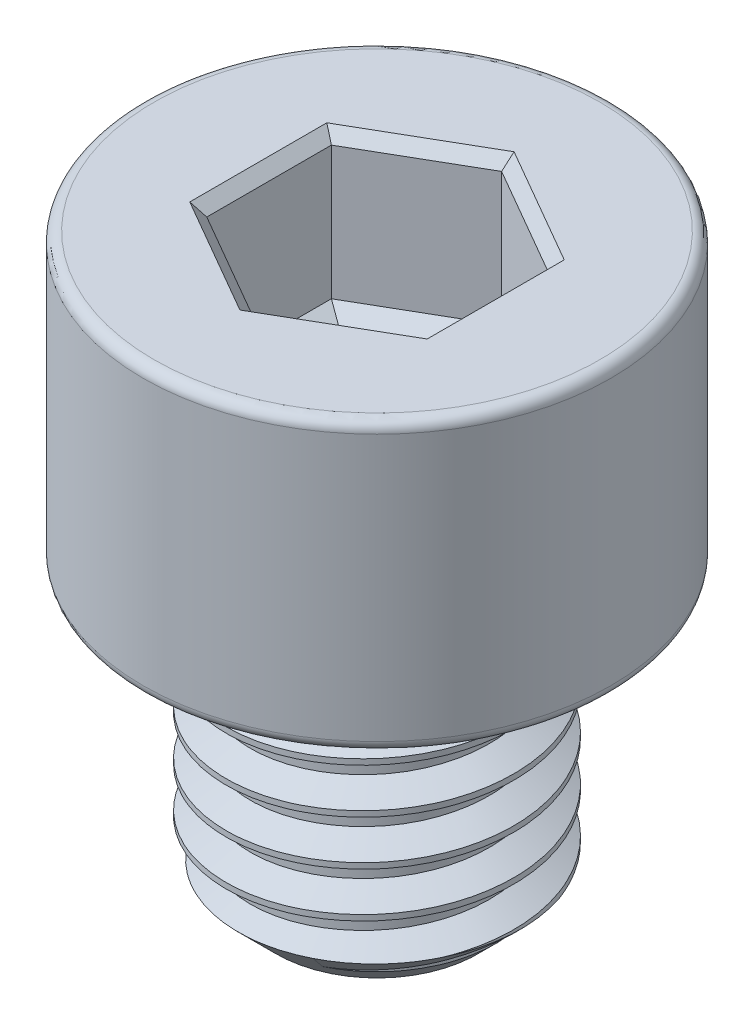
SolidWorks part; units mm, degrees
material "AISI Type A2 Tool Steel"
ref_plane "Front Plane" through (0, 0, 0) normal (0, 0, 1) x (1, 0, 0)
ref_plane "Top Plane" through (0, 0, 0) normal (0, 1, 0) x (1, 0, 0)
ref_plane "Right Plane" through (0, 0, 0) normal (1, 0, 0) x (0, 0, -1)
sketch "Sketch1" plane through (0, 0, 0) normal (0, 1, 0) x (1, 0, 0)
  circle A0 centre (0, 0) radius 4
  dimension "D1" = 8
extrude "Boss-Extrude1" add sketch "Sketch1" along normal blind 8
thread "Thread1" pitch 1.25 method cut profile "Thread Profile1" start angle 0, offset 1.25, length 0, pitch 1.25, diameter 8
ref_plane "Plane1" through (-4, 9.25, 0) normal (0, 0, 1) x (-1, 0, 0)
sketch "Thread Profile1" plane through (-4, 9.25, 0) normal (0, 0, 1) x (-1, 0, 0)
  line L0 (0, 0) -> (0, 1.25) construction
  line L11 (0, 0) -> (0, 1.0937)
  line L12 (0, 1.0937) -> (-0.6766, 0.7031)
  line L13 (-0.6766, 0.7031) -> (-0.6766, 0.3906)
  line L15 (-0.6766, 0.3906) -> (0, 0)
  line L17 (-0.6766, 0.5469) -> (0, 0.5469) construction
  point P2 (0, 0)
  dimension "Pitch" = 1.25
  dimension "Profile_Angle" = 60
  dimension "Profile_Land" = 0.3125
  dimension "Profile_Height" = 0.6766
sketch "Sketch2" plane through (0, 8, 0) normal (0, 1, 0) x (1, 0, 0)
  circle A0 centre (0, 0) radius 6.5
  dimension "D1" = 13
extrude "Boss-Extrude2" add sketch "Sketch2" along normal blind 8
sketch "Sketch5" plane through (0, 0, 0) normal (0, 0, 1) x (1, 0, 0)
  line L0 (0, 0) -> (0, 0.9986) construction
  line L1 (0, 0) -> (4.01, 0) construction
  line L2 (4.01, 0) -> (4.01, 1.2)
  line L3 (4.01, 1.2) -> (2.81, 0)
  line L4 (2.81, 0) -> (4.01, 0)
  dimension "D1" = 1.2
  dimension "D2" = 45
  dimension "D3" = 4.01
revolve "Cut-Revolve1" cut sketch "Sketch5" angle 360 about L0
fillet "Fillet1" radius 0.3 2 edges at (0, 16, 6.5) (0, 8, 6.5)
sketch "Sketch6" plane through (0, 16, 0) normal (0, 1, 0) x (1, 0, 0)
  line L1 (0, 3.4641) -> (-3, 1.7321)
  line L2 (-3, 1.7321) -> (-3, -1.7321)
  line L3 (-3, -1.7321) -> (0, -3.4641)
  line L4 (0, -3.4641) -> (3, -1.7321)
  line L5 (3, -1.7321) -> (3, 1.7321)
  line L6 (3, 1.7321) -> (0, 3.4641)
  circle A0 centre (0, 0) radius 3 construction
  dimension "D1" = 6
extrude "Cut-Extrude1" cut sketch "Sketch6" against normal blind 4
chamfer "Chamfer1" distance 0.3 angle 45 6 edges at (-3, 16, 0) (-1.5, 16, 2.5981) (1.5, 16, 2.5981) (3, 16, 0) (1.5, 16, -2.5981) (-1.5, 16, -2.5981)
sketch "Sketch7" plane through (0, 12, 0) normal (0, 1, 0) x (1, 0, 0)
  line L1 (0, 3.4641) -> (-3, 1.7321)
  line L2 (-3, 1.7321) -> (-3, -1.7321)
  line L3 (-3, -1.7321) -> (0, -3.4641)
  line L4 (0, -3.4641) -> (3, -1.7321)
  line L5 (3, -1.7321) -> (3, 1.7321)
  line L6 (3, 1.7321) -> (0, 3.4641)
  circle A0 centre (0, 0) radius 3 construction
extrude "Cut-Extrude2" cut sketch "Sketch7" against normal blind 0.4 draft 60
